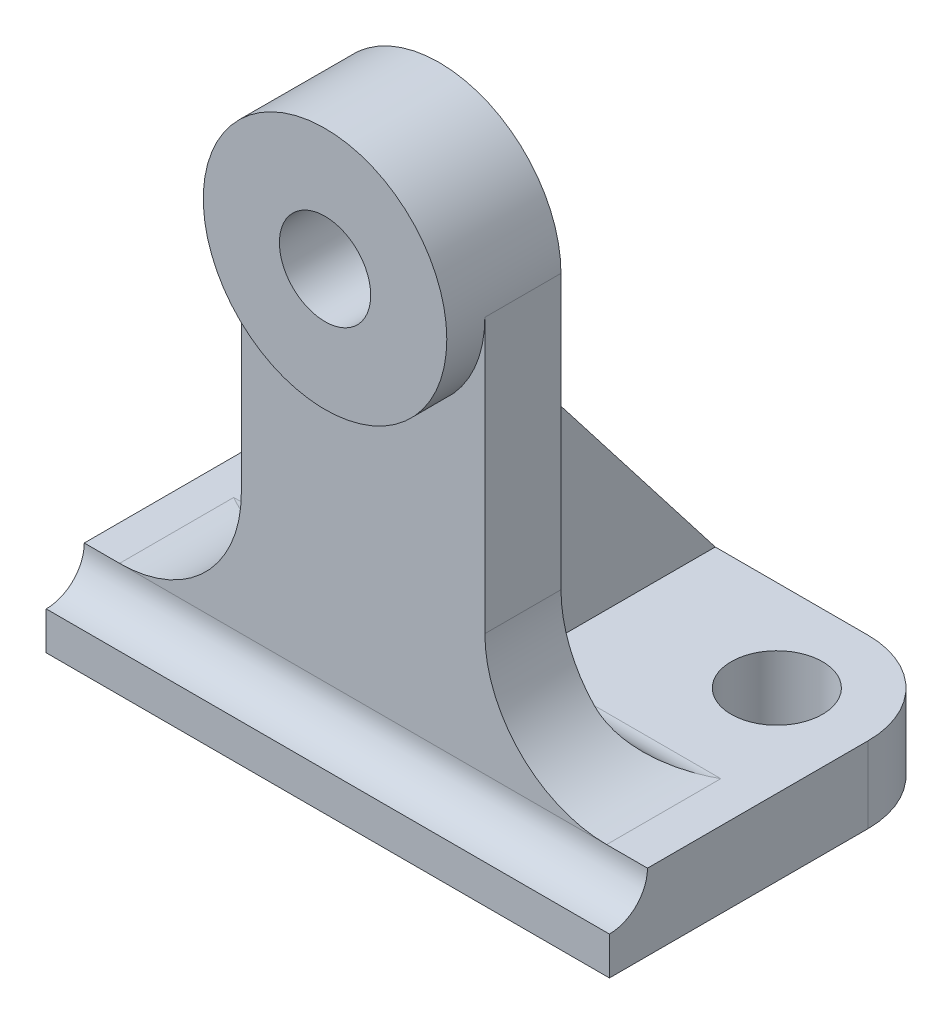
SolidWorks part; units mm, degrees
ref_plane "Front Plane" through (0, 0, 0) normal (0, 0, 1) x (1, 0, 0)
ref_plane "Top Plane" through (0, 0, 0) normal (0, 1, 0) x (1, 0, 0)
ref_plane "Right Plane" through (0, 0, 0) normal (1, 0, 0) x (0, 0, -1)
sketch "Sketch1" plane through (0, 0, 0) normal (0, 0, 1) x (1, 0, 0)
  line L0 (-47.001, -51.8058) -> (26.999, -51.8058)
  line L1 (-47.001, -51.8058) -> (-47.001, -41.8058)
  line L2 (21.6334, -41.8058) -> (26.999, -41.8058)
  line L3 (26.999, -41.8058) -> (26.999, -51.8058)
  line L5 (-47.001, -41.8058) -> (-42.3666, -41.8058)
  line L6 (-26.3666, -25.8058) -> (-26.3666, 10.1942)
  line L7 (5.6334, -25.8058) -> (5.6334, 10.1942)
  arc A0 (5.6334, 10.1942) -> (-26.3666, 10.1942) centre (-10.3666, 10.1942) ccw
  circle A1 centre (-10.3666, 10.1942) radius 6
  arc A2 (21.6334, -41.8058) -> (5.6334, -25.8058) centre (21.6334, -25.8058) cw
  arc A3 (-42.3666, -41.8058) -> (-26.3666, -25.8058) centre (-42.3666, -25.8058) ccw
extrude "Boss-Extrude1" add sketch "Sketch1" against normal blind 10
sketch "Sketch2" plane through (0, 0, 0) normal (0, 0, 1) x (1, 0, 0)
  circle A0 centre (-10.3666, 10.1942) radius 6
  circle A1 centre (-10.3666, 10.1942) radius 16
extrude "Boss-Extrude3" add sketch "Sketch2" along normal blind 5
sketch "Sketch3" plane through (0, 0, 0) normal (0, 0, 1) x (1, 0, 0)
  line L0 (-47.001, -51.8058) -> (-47.001, -46.8058)
  line L1 (-47.001, -41.8058) -> (-47.001, -51.8058) construction
  line L2 (-47.001, -46.8058) -> (26.999, -46.8058)
  line L3 (26.999, -51.8058) -> (26.999, -41.8058) construction
  line L4 (26.999, -46.8058) -> (26.999, -51.8058)
  line L5 (26.999, -51.8058) -> (-47.001, -51.8058)
extrude "Boss-Extrude5" add sketch "Sketch3" along normal blind 5
fillet "Fillet4" radius 5 1 edges at (-10.001, -46.8058, 0)
sketch "Sketch5" plane through (0, 0, -10) normal (0, 0, -1) x (-1, 0, 0)
  line L1 (-26.999, -41.8058) -> (47.001, -41.8058)
  line L2 (-26.999, -41.8058) -> (-26.999, -51.8058)
  line L3 (-26.999, -51.8058) -> (47.001, -51.8058)
  line L4 (47.001, -41.8058) -> (47.001, -51.8058)
extrude "Boss-Extrude8" add sketch "Sketch5" along normal blind 31
sketch "Sketch13" plane through (0, -41.8058, 0) normal (0, 1, 0) x (1, 0, 0)
  line L1 (-47.001, 41) -> (26.999, 41) construction
  line L2 (-10.0918, 41) -> (-15.0918, 41)
  line L3 (-10.0918, 41) -> (-5.0918, 41)
  line L4 (-5.0918, 41) -> (-5.0918, 10)
  line L5 (-42.3666, 10) -> (21.6334, 10) construction
  line L6 (-15.0918, 41) -> (-15.0918, 10)
  line L7 (-15.0918, 10) -> (-5.0918, 10)
extrude "Boss-Extrude10" add sketch "Sketch13" along normal blind 40
sketch "Sketch14" plane through (-15.0918, 0, 0) normal (-1, 0, 0) x (0, 0, 1)
  line L0 (-41, -41.8058) -> (-10, -1.8058)
  line L1 (-41, -41.8058) -> (-41, -1.8058)
  line L2 (-41, -1.8058) -> (-10, -1.8058)
extrude "Cut-Extrude1" cut sketch "Sketch14" against normal blind 10
fillet "Fillet5" radius 5 1 edges
fillet "Fillet6" radius 5 1 edges
fillet "Fillet7" radius 12 1 edges at (26.999, -46.8058, -41)
fillet "Fillet8" radius 12 1 edges at (-47.001, -46.8058, -41)
sketch "Sketch16" plane through (0, -41.8058, 0) normal (0, 1, 0) x (1, 0, 0)
  circle A0 centre (14.999, 29) radius 6
extrude "Cut-Extrude2" cut sketch "Sketch16" against normal blind 10
sketch "Sketch17" plane through (0, -41.8058, 0) normal (0, 1, 0) x (1, 0, 0)
  circle A0 centre (-35.001, 29) radius 6
extrude "Cut-Extrude3" cut sketch "Sketch17" against normal blind 10
